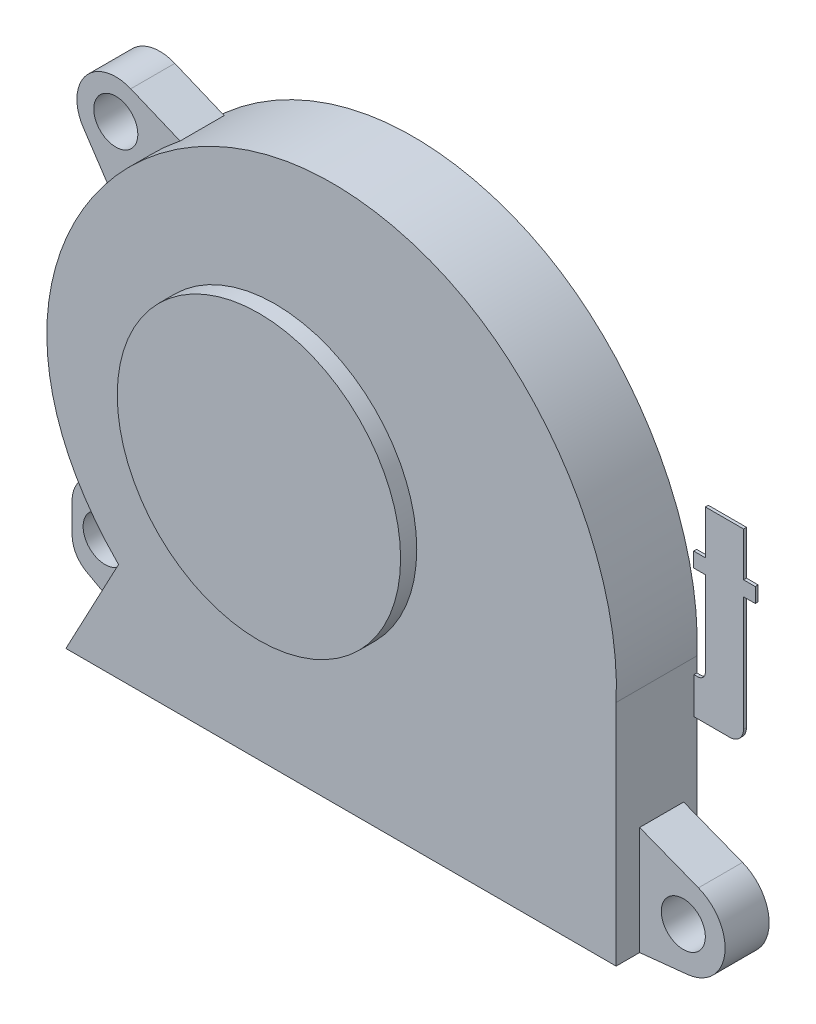
SolidWorks part; units mm, degrees
ref_plane "Ebene vorne" through (0, 0, 0) normal (0, 0, 1) x (1, 0, 0)
ref_plane "Ebene oben" through (0, 0, 0) normal (0, 1, 0) x (1, 0, 0)
ref_plane "Ebene rechts" through (0, 0, 0) normal (1, 0, 0) x (0, 0, -1)
sketch "Skizze1" plane through (0, 0, 0) normal (0, 0, 1) x (1, 0, 0)
  line L0 (295.6363, 873.8245) -> (1883.1214, 873.8245) construction
  line L1 (41.5796, 57.8629) -> (1.5796, 57.8629) construction
  line L2 (23.2299, -17.8) -> (23.2299, -2.2475)
  line L3 (-10.6632, -11.0564) -> (-14.2488, -17.8)
  line L4 (-14.2488, -17.8) -> (23.2299, -17.8)
  line L5 (-8.069, 14.4239) -> (-11.4304, 15.8221)
  line L6 (-14.6531, 11.9064) -> (-12.8123, 9.1437)
  line L7 (23.2299, -10.4185) -> (27.2377, -11.9772)
  line L8 (26.5007, -17.4597) -> (23.2299, -17.8)
  line L9 (-13.2158, -7.8638) -> (-14.3633, -8.5823)
  line L10 (-15.4233, -10.6846) -> (-15.4233, -12.5076)
  line L11 (-14.4348, -14.1784) -> (-12.8005, -15.0762)
  line L12 (23.2299, -3.2525) -> (23.4812, -3.2525)
  line L13 (24.0081, -2.7256) -> (24.0081, 3.0279)
  line L14 (24.0081, 3.0279) -> (23.2081, 3.0279)
  line L15 (23.2081, 3.0279) -> (23.2081, 4.0279)
  line L16 (23.2081, 4.0279) -> (24.0081, 4.0279)
  line L17 (24.0081, 4.0279) -> (24.0081, 7.0279)
  line L18 (24.0081, 7.0279) -> (26.6081, 7.0279)
  line L19 (26.6081, 7.0279) -> (26.6081, 4.0279)
  line L20 (26.6081, 4.0279) -> (27.4081, 4.0279)
  line L21 (27.4081, 4.0279) -> (27.4081, 3.0279)
  line L22 (27.4081, 3.0279) -> (26.6081, 3.0279)
  line L23 (26.6081, 3.0279) -> (26.6081, -4.7903)
  line L24 (25.665, -5.7334) -> (23.2299, -5.7334)
  circle A1 centre (0, 0) radius 12.15
  circle A2 centre (26.2062, -14.6294) radius 1.5
  circle A3 centre (-13.1762, -11.6185) radius 1.5
  circle A4 centre (-12.448, 13.3756) radius 1.5
  arc A5 (-11.4304, 15.8221) -> (-14.6531, 11.9064) centre (-12.448, 13.3756) ccw
  arc A6 (27.2377, -11.9772) -> (26.5007, -17.4597) centre (26.2062, -14.6294) cw
  arc A7 (-14.3633, -8.5823) -> (-15.4233, -10.6846) centre (-13.1568, -10.509) ccw
  arc A8 (-15.4233, -12.5076) -> (-14.4348, -14.1784) centre (-13.5169, -12.5076) ccw
  circle A9 centre (0, 0) radius 9.65
  arc A10 (23.4812, -3.2525) -> (24.0081, -2.7256) centre (23.4812, -2.7256) ccw
  arc A11 (26.6081, -4.7903) -> (25.665, -5.7334) centre (25.665, -4.7903) cw
  spline S0 degree 3 poles (23.2299, -2.2475) (23.5705, 5.0184) (17.4359, 16.5094) (2.3155, 19.7739) (-13.9174, 13.222) (-19.3064, -2.3385) (-10.6632, -11.0564) knots 0 0 0 0 0.303536 0.457029 0.601755 1 1 1 1
  dimension "D1" = 40
  dimension "D2" = 17.8
  dimension "D3" = 24.3
  dimension "D4" = 19.3
  dimension "D6" = 3
  dimension "D7" = 2.6
  dimension "D5" = 62
  dimension "D8" = 0.8
  dimension "D9" = 1
  dimension "D10" = 3
extrude "Aufsatz-Linear austragen1" add sketch "Skizze1" along normal blind 5.5 contours L2 S0 L3 L4 A1 | A1 A9 region at (4.4905, -17.2672, 0) region at (-11.8063, 0, 0)
extrude "Aufsatz-Linear austragen2" add sketch "Skizze1<3>" along normal blind 6.6 contours A9 region at (0, 0, 0)
sketch "Skizze1<3>" plane through (0, 0, 0) normal (0, 0, 1) x (1, 0, 0) same geometry as "Skizze1"
extrude "Aufsatz-Linear austragen3" add sketch "Skizze1<5>" along normal blind 3 from offset 0.9 contours S0 L5 A5 L6 A4 | A6 L7 L2 L8 A2 | S0 L9 A7 L10 A8 L11 L3 A3 region at (23.3239, -14.1092, 0) region at (-13.576, -14.5516, 0) region at (-10.7393, 12.052, 0)
sketch "Skizze1<5>" plane through (0, 0, 0) normal (0, 0, 1) x (1, 0, 0) same geometry as "Skizze1"
extrude "Aufsatz-Linear austragen4" add sketch "Skizze1<6>" along normal blind 0.2 contours A11 L23 L22 L21 L20 L19 L18 L17 L16 L15 L14 L13 A10 L12 L2 L24 region at (25.211, 0.528, 0)
sketch "Skizze1<6>" plane through (0, 0, 0) normal (0, 0, 1) x (1, 0, 0) same geometry as "Skizze1"
